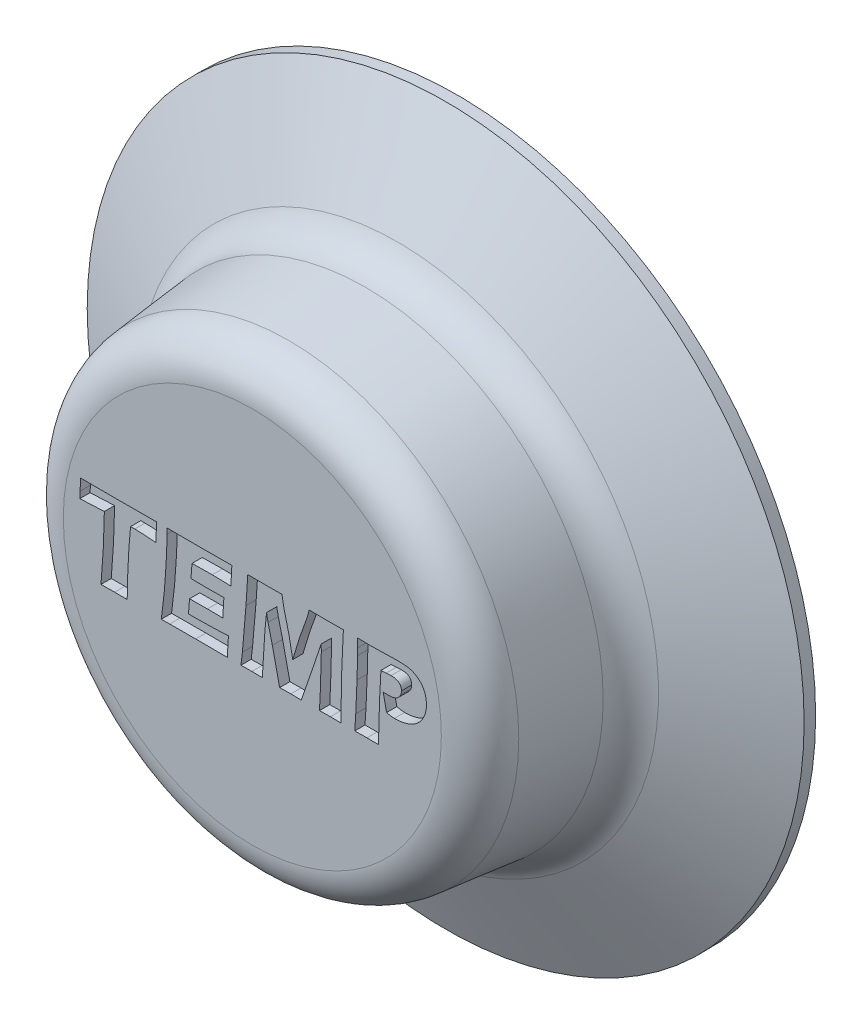
SolidWorks part; units mm, degrees
ref_plane "Piano frontale" through (0, 0, 0) normal (0, 0, 1) x (1, 0, 0)
ref_plane "Piano superiore" through (0, 0, 0) normal (0, 1, 0) x (1, 0, 0)
ref_plane "Piano destro" through (0, 0, 0) normal (1, 0, 0) x (0, 0, -1)
sketch "Schizzo1" plane through (0, 0, 0) normal (0, 0, 1) x (1, 0, 0)
  circle A0 centre (0, 0) radius 17.5
  dimension "D1" = 35
extrude "Estrusione-Estrusione1" add sketch "Schizzo1" along normal blind 10
sketch "Schizzo2" plane through (0, 0, 10) normal (0, 0, 1) x (1, 0, 0)
  circle A0 centre (0, 0) radius 12.5
  circle A1 centre (0, 0) radius 17.5 construction
  circle A2 centre (0, 0) radius 17.5
  dimension "D1" = 5
extrude "Taglio-Estrusione1" cut sketch "Schizzo2" against normal offset from surface (7 mm away) 3 up to face at (17.5, 0, 0)
chamfer "Smusso1" distance 5 angle 26 1 edges at (17.5, 0, 3) first distance on face at (17.5, 0, 3)
chamfer "Smusso2" distance 14 angle 6 1 edges at (12.5, 0, 10) first distance on face at (12.5, 0, 3)
fillet "Raccordo1" radius 2 2 edges at (-11.7245, 0, 3.3782) (11.0285, 0, 10)
sketch "Schizzo3" plane through (0, 0, 10) normal (0, 0, 1) x (1, 0, 0)
  line L0 (-9.2277, -1.8928) -> (9.2277, -1.8928) construction
  text T0 "TEMP" font "Eras Bold ITC" height 4
  point P2 (0, -1.8928)
extrude "Taglio-Estrusione2" cut sketch "Schizzo3" against normal blind 0.5
sketch "Schizzo4" plane through (0, 0, 0) normal (0, 0, -1) x (-1, 0, 0)
  line L0 (0, 17.5) -> (0, 13.5) construction
  line L1 (-0.5, 17.5) -> (-0.5, 13.5)
  line L2 (0.5, 17.5) -> (0.5, 13.5)
  line L3 (0.5, 17.5) -> (-0.5, 17.5)
  line L4 (0.5, 13.5) -> (-0.5, 13.5)
  circle A0 centre (0, 0) radius 17.5 construction
  dimension "D1" = 4
  dimension "D2" = 0.5
  dimension "D3" = 0.5
sketch "Schizzo5" plane through (0, 0, 0) normal (0, 0, -1) x (-1, 0, 0)
  line L0 (1.6, 2.5377) -> (1.6, -2.5377)
  arc A0 (1.6, 2.5377) -> (1.6, -2.5377) centre (0, 0) ccw
  dimension "D1" = 6
  dimension "D2" = 1.6
extrude "Taglio-Estrusione3" cut sketch "Schizzo5" against normal offset from surface (8 mm away) 2 up to face at (9.2277, 0, 10)
chamfer "Smusso3" distance 2 angle 45 2 edges at (-1.6, 0, 0) (3, 0, 0)
